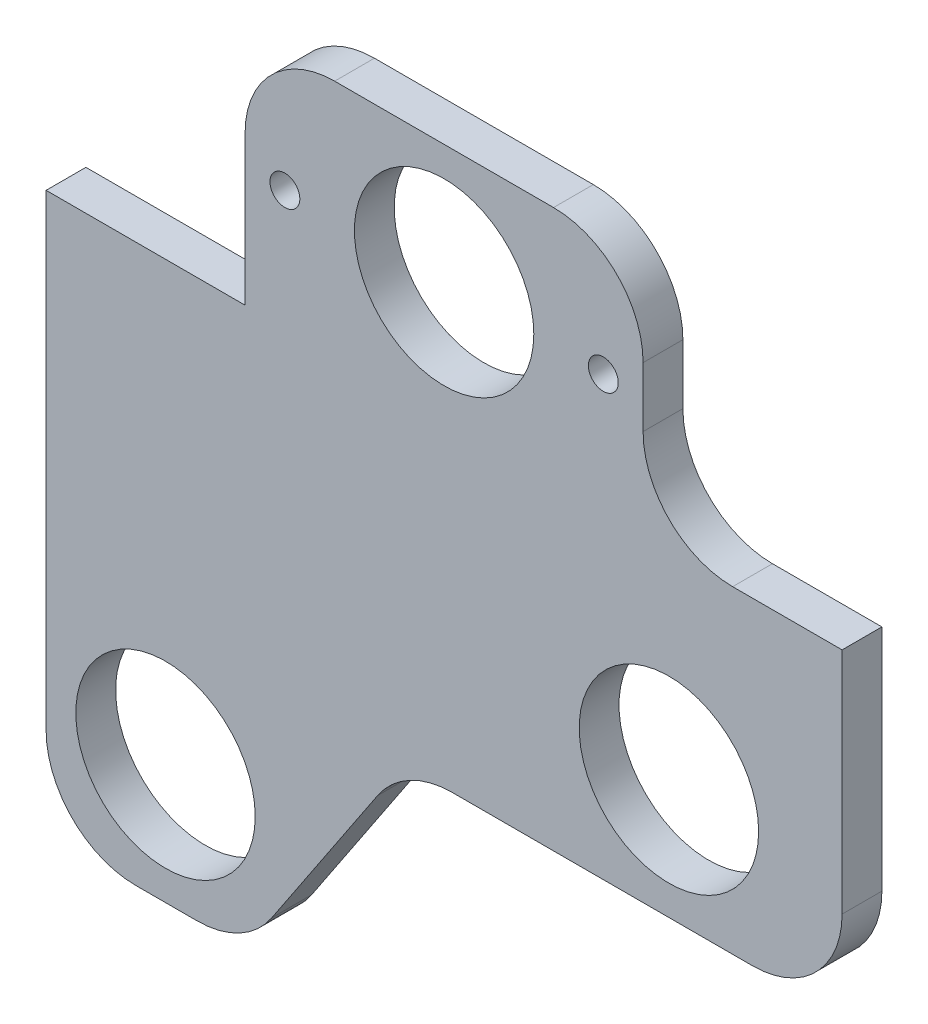
SolidWorks part; units mm, degrees
ref_plane "Front Plane" through (0, 0, 0) normal (0, 0, 1) x (1, 0, 0)
ref_plane "Top Plane" through (0, 0, 0) normal (0, 1, 0) x (1, 0, 0)
ref_plane "Right Plane" through (0, 0, 0) normal (1, 0, 0) x (0, 0, -1)
sketch "Sketch1" plane through (0, 0, 0) normal (0, 0, 1) x (1, 0, 0)
  line L0 (63.5, -6.35) -> (-6.35, -6.35)
  line L1 (-63.5, 44.45) -> (63.5, 44.45)
  line L2 (-63.5, 44.45) -> (-63.5, -44.45)
  line L3 (-63.5, -44.45) -> (63.5, -44.45)
  line L4 (63.5, 44.45) -> (63.5, -44.45)
  line L5 (-63.5, 44.45) -> (63.5, -44.45) construction
  line L6 (-63.5, -44.45) -> (63.5, 44.45) construction
  line L7 (-6.35, -6.35) -> (-31.75, -44.45)
  circle A0 centre (-44.45, -25.4) radius 14.3129
  circle A1 centre (35.8719, 12.7) radius 14.3129
  point P0 (0, 0)
  dimension "D1" = 28.6258
  dimension "D2" = 28.6258
  dimension "D3" = 88.9
  dimension "D4" = 19.05
  dimension "D5" = 57.15
  dimension "D6" = 88.9
  dimension "D7" = 19.05
  dimension "D8" = 127
  dimension "D9" = 38.1
  dimension "D10" = 31.75
  dimension "D11" = 57.15
extrude "Boss-Extrude1" add sketch "Sketch1" along normal blind 6.35 contours L7 L0 L4 L1 L2 L3 A1 A0 region at (-9.2383, 13.2886, 0)
fillet "Fillet1" radius 14.2875 4 edges at (63.5, -6.35, 3.175) (-6.35, -6.35, 3.175) (-31.75, -44.45, 3.175) (-63.5, -44.45, 3.175)
sketch "Sketch2" plane through (0, 0, 6.35) normal (0, 0, 1) x (1, 0, 0)
  line L0 (-63.5, 44.45) -> (63.5, 44.45) construction
  line L1 (-31.75, 44.45) -> (31.75, 44.45)
  line L2 (-31.75, 44.45) -> (-31.75, 82.55)
  line L3 (-31.75, 82.55) -> (31.75, 82.55)
  line L4 (31.75, 44.45) -> (31.75, 82.55)
  line L5 (-63.5, 44.45) -> (-63.5, -30.1625) construction
  dimension "D1" = 38.1
  dimension "D2" = 31.75
  dimension "D3" = 63.5
extrude "Boss-Extrude2" add sketch "Sketch2" against normal blind 6.35
fillet "Fillet2" radius 14.2875 3 edges at (-31.75, 82.55, 3.175) (31.75, 82.55, 3.175) (31.75, 44.45, 3.175)
sketch "Sketch3" plane through (0, 0, 6.35) normal (0, 0, 1) x (1, 0, 0)
  line L1 (17.4625, 82.55) -> (-17.4625, 82.55) construction
  circle A0 centre (0, 63.5) radius 14.3129
  circle A1 centre (35.8719, 12.7) radius 14.3129 construction
  dimension "D1" = 28.6258
  dimension "D2" = 35.8719
  dimension "D3" = 19.05
extrude "Cut-Extrude1" cut sketch "Sketch3" against normal through all
sketch "Sketch4" plane through (0, 0, 6.35) normal (0, 0, 1) x (1, 0, 0)
  circle A0 centre (-25.4, 63.5) radius 2.3813
  circle A1 centre (25.4, 63.5) radius 2.3813
  circle A2 centre (0, 63.5) radius 14.2875
  circle A3 centre (0, 63.5) radius 25.4 construction
  point P7 (0, 0)
  dimension "D1" = 50.8
  dimension "D2" = 4.7625
  dimension "D3" = 4.7625
extrude "Cut-Extrude2" cut sketch "Sketch4" against normal through all
